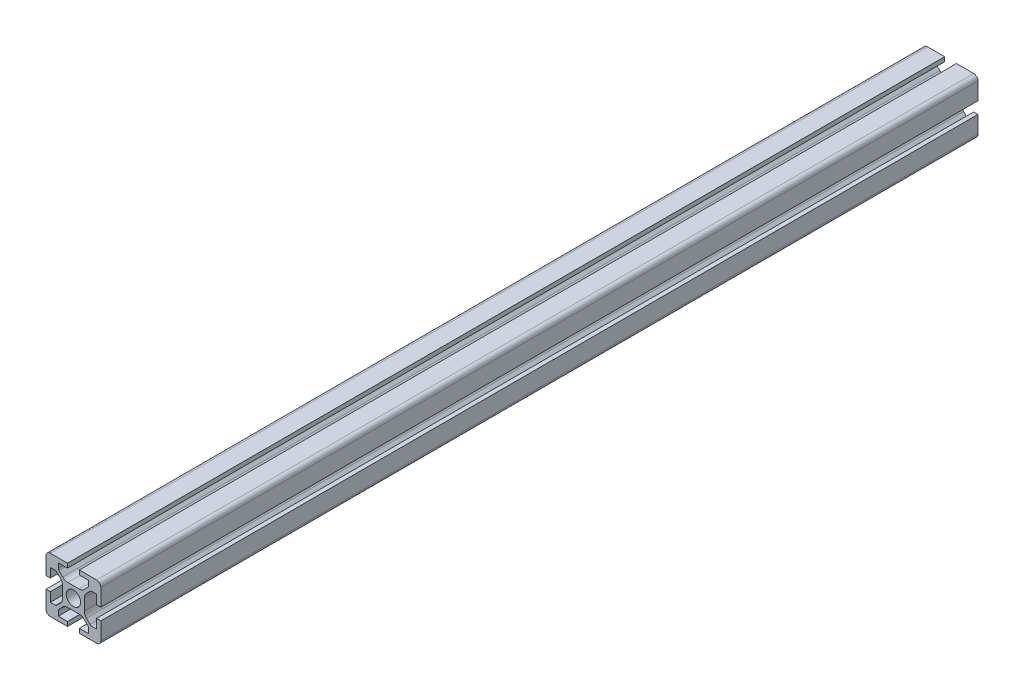
SolidWorks part; units mm, degrees
note: '?' marks a value the reader was unsure of.
ref_plane "Front Plane" through (0, 0, 0) normal (0, 0, 1) x (1, 0, 0)
ref_plane "Top Plane" through (0, 0, 0) normal (0, 1, 0) x (1, 0, 0)
ref_plane "Right Plane" through (0, 0, 0) normal (1, 0, 0) x (0, 0, -1)
sketch "Sketch1" plane through (0, 0, 0) normal (0, 0, 1) x (1, 0, 0)
  line L0 (-19.05, -4.1) -> (-19.05, -16.05)
  line L1 (-16.05, -19.05) -> (-4.1, -19.05)
  line L2 (-4.1, -19.05) -> (-4.1, -16.05)
  line L3 (-4.1, -16.05) -> (-10.5, -16.05)
  line L4 (-10.5, -16.05) -> (-10.5, -12.7127)
  line L5 (-10.0313, -11.5814) -> (-7.4645, -9.0145)
  line L6 (-3.9289, -7.55) -> (3.9289, -7.55)
  line L7 (7.4645, -9.0145) -> (10.0313, -11.5814)
  line L8 (10.5, -12.7127) -> (10.5, -16.05)
  line L9 (10.5, -16.05) -> (4.1, -16.05)
  line L10 (4.1, -16.05) -> (4.1, -19.05)
  line L11 (4.1, -19.05) -> (16.05, -19.05)
  line L12 (19.05, -16.05) -> (19.05, -4.1)
  line L13 (19.05, -4.1) -> (16.05, -4.1)
  line L14 (16.05, -4.1) -> (16.05, -10.5)
  line L15 (16.05, -10.5) -> (12.7127, -10.5)
  line L16 (11.5814, -10.0313) -> (9.0145, -7.4645)
  line L17 (7.55, -3.9289) -> (7.55, 3.9289)
  line L18 (9.0145, 7.4645) -> (11.5814, 10.0313)
  line L19 (12.7127, 10.5) -> (16.05, 10.5)
  line L20 (16.05, 10.5) -> (16.05, 4.1)
  line L21 (16.05, 4.1) -> (19.05, 4.1)
  line L22 (19.05, 4.1) -> (19.05, 16.05)
  line L23 (16.05, 19.05) -> (4.1, 19.05)
  line L24 (4.1, 19.05) -> (4.1, 16.05)
  line L25 (4.1, 16.05) -> (10.5, 16.05)
  line L26 (10.5, 16.05) -> (10.5, 12.7127)
  line L27 (10.0313, 11.5814) -> (7.4645, 9.0145)
  line L28 (3.9289, 7.55) -> (-3.9289, 7.55)
  line L29 (-7.4645, 9.0145) -> (-10.0313, 11.5814)
  line L30 (-10.5, 12.7127) -> (-10.5, 16.05)
  line L31 (-10.5, 16.05) -> (-4.1, 16.05)
  line L32 (-4.1, 16.05) -> (-4.1, 19.05)
  line L33 (-4.1, 19.05) -> (-16.05, 19.05)
  line L34 (-19.05, 16.05) -> (-19.05, 4.1)
  line L35 (-19.05, 4.1) -> (-16.05, 4.1)
  line L36 (-16.05, 4.1) -> (-16.05, 10.5)
  line L37 (-16.05, 10.5) -> (-12.7127, 10.5)
  line L38 (-11.5814, 10.0313) -> (-9.0145, 7.4645)
  line L39 (-7.55, 3.9289) -> (-7.55, -3.9289)
  line L40 (-9.0145, -7.4645) -> (-11.5814, -10.0313)
  line L41 (-12.7127, -10.5) -> (-16.05, -10.5)
  line L42 (-16.05, -10.5) -> (-16.05, -4.1)
  line L43 (-16.05, -4.1) -> (-19.05, -4.1)
  arc A0 (-19.05, -16.05) -> (-16.05, -19.05) centre (-16.05, -16.05) ccw
  arc A1 (-10.5, -12.7127) -> (-10.0313, -11.5814) centre (-8.9002, -12.7127) cw
  arc A2 (-7.4645, -9.0145) -> (-3.9289, -7.55) centre (-3.9289, -12.55) cw
  arc A3 (3.9289, -7.55) -> (7.4645, -9.0145) centre (3.9289, -12.55) cw
  arc A4 (10.0313, -11.5814) -> (10.5, -12.7127) centre (8.9002, -12.7127) cw
  arc A5 (16.05, -19.05) -> (19.05, -16.05) centre (16.05, -16.05) ccw
  arc A6 (12.7127, -10.5) -> (11.5814, -10.0313) centre (12.7127, -8.9002) cw
  arc A7 (9.0145, -7.4645) -> (7.55, -3.9289) centre (12.55, -3.9289) cw
  arc A8 (7.55, 3.9289) -> (9.0145, 7.4645) centre (12.55, 3.9289) cw
  arc A9 (11.5814, 10.0313) -> (12.7127, 10.5) centre (12.7127, 8.9002) cw
  arc A10 (19.05, 16.05) -> (16.05, 19.05) centre (16.05, 16.05) ccw
  arc A11 (10.5, 12.7127) -> (10.0313, 11.5814) centre (8.9002, 12.7127) cw
  arc A12 (7.4645, 9.0145) -> (3.9289, 7.55) centre (3.9289, 12.55) cw
  arc A13 (-3.9289, 7.55) -> (-7.4645, 9.0145) centre (-3.9289, 12.55) cw
  arc A14 (-10.0313, 11.5814) -> (-10.5, 12.7127) centre (-8.9002, 12.7127) cw
  arc A15 (-16.05, 19.05) -> (-19.05, 16.05) centre (-16.05, 16.05) ccw
  arc A16 (-12.7127, 10.5) -> (-11.5814, 10.0313) centre (-12.7127, 8.9002) cw
  arc A17 (-9.0145, 7.4645) -> (-7.55, 3.9289) centre (-12.55, 3.9289) cw
  arc A18 (-7.55, -3.9289) -> (-9.0145, -7.4645) centre (-12.55, -3.9289) cw
  arc A19 (-11.5814, -10.0313) -> (-12.7127, -10.5) centre (-12.7127, -8.9002) cw
  circle A20 centre (0, 0) radius 5
extrude "Boss-Extrude1" add sketch "Sketch1" along a picked direction on the side of the normal mid plane 609.6
sketch "Sketch2" plane through (0, 0, 0) normal (0, 0, 1) x (1, 0, 0)
  line L0 (-17.55, -12.5) -> (-17.55, -16.05)
  line L1 (-16.05, -17.55) -> (-12.5, -17.55)
  line L2 (-12, -17.05) -> (-12, -12.5)
  line L3 (-12.5, -12) -> (-17.05, -12)
  arc A0 (-17.55, -16.05) -> (-16.05, -17.55) centre (-16.05, -16.05) ccw
  arc A1 (-12.5, -17.55) -> (-12, -17.05) centre (-12.5, -17.05) ccw
  arc A2 (-12, -12.5) -> (-12.5, -12) centre (-12.5, -12.5) ccw
  arc A3 (-17.05, -12) -> (-17.55, -12.5) centre (-17.05, -12.5) ccw
sketch "Sketch3" plane through (0, 0, 0) normal (0, 0, 1) x (1, 0, 0)
  line L0 (12.5, -17.55) -> (16.05, -17.55)
  line L1 (17.55, -16.05) -> (17.55, -12.5)
  line L2 (17.05, -12) -> (12.5, -12)
  line L3 (12, -12.5) -> (12, -17.05)
  arc A0 (12, -17.05) -> (12.5, -17.55) centre (12.5, -17.05) ccw
  arc A1 (16.05, -17.55) -> (17.55, -16.05) centre (16.05, -16.05) ccw
  arc A2 (17.55, -12.5) -> (17.05, -12) centre (17.05, -12.5) ccw
  arc A3 (12.5, -12) -> (12, -12.5) centre (12.5, -12.5) ccw
sketch "Sketch4" plane through (0, 0, 0) normal (0, 0, 1) x (1, 0, 0)
  line L0 (-6.05, 1.0672) -> (-6.05, -1.191)
  line L1 (-6.05, -1.191) -> (-4.8565, -1.1891)
  line L2 (-4.2083, -2.7) -> (-6.05, -2.7)
  line L3 (-6.05, -2.7) -> (-6.05, -5.05)
  line L4 (-5.05, -6.05) -> (-2.7, -6.05)
  line L5 (-2.7, -6.05) -> (-2.7, -4.2083)
  line L6 (-1.15, -4.866) -> (-1.15, -6.05)
  line L7 (-1.15, -6.05) -> (1.15, -6.05)
  line L8 (1.15, -6.05) -> (1.15, -4.866)
  line L9 (2.7, -4.2083) -> (2.7, -6.05)
  line L10 (2.7, -6.05) -> (5.05, -6.05)
  line L11 (6.05, -5.05) -> (6.05, -2.7)
  line L12 (6.05, -2.7) -> (4.2083, -2.7)
  line L13 (4.8603, -1.1736) -> (6.05, -1.1717)
  line L14 (6.05, -1.1717) -> (6.05, 1.1063)
  line L15 (6.05, 1.1063) -> (4.8769, 1.1025)
  line L16 (4.2083, 2.7) -> (6.05, 2.7)
  line L17 (6.05, 2.7) -> (6.05, 5.05)
  line L18 (5.05, 6.05) -> (2.7, 6.05)
  line L19 (2.7, 6.05) -> (2.7, 4.2083)
  line L20 (1.15, 4.866) -> (1.15, 6.05)
  line L21 (1.15, 6.05) -> (-1.15, 6.05)
  line L22 (-1.15, 6.05) -> (-1.15, 4.866)
  line L23 (-2.7, 4.2083) -> (-2.7, 6.05)
  line L24 (-2.7, 6.05) -> (-5.05, 6.05)
  line L25 (-6.05, 5.05) -> (-6.05, 2.7)
  line L26 (-6.05, 2.7) -> (-4.2083, 2.7)
  line L27 (-4.8839, 1.071) -> (-6.05, 1.0672)
  arc A0 (-4.8565, -1.1891) -> (-4.2083, -2.7) centre (0, 0) ccw
  arc A1 (-6.05, -5.05) -> (-5.05, -6.05) centre (-5.05, -5.05) ccw
  arc A2 (-2.7, -4.2083) -> (-1.15, -4.866) centre (0, 0) ccw
  arc A3 (1.15, -4.866) -> (2.7, -4.2083) centre (0, 0) ccw
  arc A4 (5.05, -6.05) -> (6.05, -5.05) centre (5.05, -5.05) ccw
  arc A5 (4.2083, -2.7) -> (4.8603, -1.1736) centre (0, 0) ccw
  arc A6 (4.8769, 1.1025) -> (4.2083, 2.7) centre (0, 0) ccw
  arc A7 (6.05, 5.05) -> (5.05, 6.05) centre (5.05, 5.05) ccw
  arc A8 (2.7, 4.2083) -> (1.15, 4.866) centre (0, 0) ccw
  arc A9 (-1.15, 4.866) -> (-2.7, 4.2083) centre (0, 0) ccw
  arc A10 (-5.05, 6.05) -> (-6.05, 5.05) centre (-5.05, 5.05) ccw
  arc A11 (-4.2083, 2.7) -> (-4.8839, 1.071) centre (0, 0) ccw
sketch "Sketch5" plane through (0, 0, 0) normal (0, 0, 1) x (1, 0, 0)
  line L0 (12, 17.05) -> (12, 12.5)
  line L1 (12.5, 12) -> (17.05, 12)
  line L2 (17.55, 12.5) -> (17.55, 16.05)
  line L3 (16.05, 17.55) -> (12.5, 17.55)
  arc A0 (12, 12.5) -> (12.5, 12) centre (12.5, 12.5) ccw
  arc A1 (17.05, 12) -> (17.55, 12.5) centre (17.05, 12.5) ccw
  arc A2 (17.55, 16.05) -> (16.05, 17.55) centre (16.05, 16.05) ccw
  arc A3 (12.5, 17.55) -> (12, 17.05) centre (12.5, 17.05) ccw
sketch "Sketch6" plane through (0, 0, 0) normal (0, 0, 1) x (1, 0, 0)
  line L0 (-17.05, 12) -> (-12.5, 12)
  line L1 (-12, 12.5) -> (-12, 17.05)
  line L2 (-12.5, 17.55) -> (-16.05, 17.55)
  line L3 (-17.55, 16.05) -> (-17.55, 12.5)
  arc A0 (-17.55, 12.5) -> (-17.05, 12) centre (-17.05, 12.5) ccw
  arc A1 (-12.5, 12) -> (-12, 12.5) centre (-12.5, 12.5) ccw
  arc A2 (-12, 17.05) -> (-12.5, 17.55) centre (-12.5, 17.05) ccw
  arc A3 (-16.05, 17.55) -> (-17.55, 16.05) centre (-16.05, 16.05) ccw
extrude "Cut-Extrude1" cut sketch "Sketch2" against normal blind 6000
extrude "Cut-Extrude2" cut sketch "Sketch3" against normal blind 6000
extrude "Cut-Extrude3" cut sketch "Sketch4" against normal blind 6000
extrude "Cut-Extrude4" cut sketch "Sketch5" against normal blind 6000
extrude "Cut-Extrude5" cut sketch "Sketch6" against normal blind 6000
ref_plane "Plane1" through (0, 19.05, 0) normal (0, 1, 0) x (-1, 0, 0)
ref_plane "Plane2" through (0, -19.05, 0) normal (0, -1, 0) x (1, 0, 0)
ref_plane "Plane3" through (19.05, 0, 0) normal (1, 0, 0) x (0, 0, -1)
ref_plane "Plane4" through (-19.05, 0, 0) normal (-1, 0, 0) x (0, 0, 1)
ref_plane "Plane5" through (0, 0, 0) normal (0, 0, 1) x (1, 0, 0)
ref_plane "Plane6" through (0, 0, 0) normal (0, 0, 1) x (1, 0, 0)
ref_plane "Plane7" through (0, 0, 0) normal (0, 0, 1) x (1, 0, 0)
ref_plane "Plane8" through (0, 0, -50) normal (0, 0, 1) x (1, 0, 0)
ref_plane "Plane9" through (0, 0, -50) normal (0, 0, 1) x (1, 0, 0)
ref_plane "Plane10" through (0, 0, -50) normal (0, 0, 1) x (1, 0, 0)
ref_plane "side_4d XY" through (0, 0, 0) normal (0, 0, 1) x (1, 0, 0)
ref_plane "side_4d XZ" through (-19.05, 0, 0) normal (-1, 0, 0) x (0, 0, 1)
ref_plane "side_4d YZ" through (0, 0, 0) normal (0, -1, 0) x (1, 0, 0)
ref_axis "side_4d X" through (-19.05, 50, 0) along (0, -1, 0)?
ref_axis "side_4d Y" through (-80.9, 0, 0) along (1, 0, 0)?
ref_axis "side_4d Z" through (-19.05, 0, 50) along (0, 0, -1)?
sketch3d "side_4d"
  point P0 (-19.05, 0, 0)
ref_plane "side_1a XY" through (0, 0, 0) normal (0, 0, 1) x (1, 0, 0)
ref_plane "side_1a XZ" through (0, 19.05, 0) normal (0, -1, 0) x (1, 0, 0)
ref_plane "side_1a YZ" through (0, 0, 0) normal (1, 0, 0) x (0, 0, -1)
ref_axis "side_1a X" through (-80.9, 19.05, 0) along (1, 0, 0)?
ref_axis "side_1a Y" through (0, -50, 0) along (0, 1, 0)?
ref_axis "side_1a Z" through (0, 19.05, 80.9) along (0, 0, -1)?
sketch3d "side_1a"
  point P0 (0, 19.05, 0)
ref_plane "side_2b XY" through (0, 0, 0) normal (0, 0, 1) x (1, 0, 0)
ref_plane "side_2b XZ" through (19.05, 0, 0) normal (1, 0, 0) x (0, 0, -1)
ref_plane "side_2b YZ" through (0, 0, 0) normal (0, 1, 0) x (-1, 0, 0)
ref_axis "side_2b X" through (19.05, -50, 0) along (0, 1, 0)?
ref_axis "side_2b Y" through (80.9, 0, 0) along (-1, 0, 0)?
ref_axis "side_2b Z" through (19.05, 0, 50) along (0, 0, -1)?
sketch3d "side_2b"
  point P0 (19.05, 0, 0)
ref_plane "side_3c XY" through (0, 0, 0) normal (0, 0, 1) x (1, 0, 0)
ref_plane "side_3c XZ" through (0, -19.05, 0) normal (0, 1, 0) x (-1, 0, 0)
ref_plane "side_3c YZ" through (0, 0, 0) normal (-1, 0, 0) x (0, 0, 1)
ref_axis "side_3c X" through (80.9, -19.05, 0) along (-1, 0, 0)?
ref_axis "side_3c Y" through (0, 50, 0) along (0, -1, 0)?
ref_axis "side_3c Z" through (0, -19.05, 80.9) along (0, 0, -1)?
sketch3d "side_3c"
  point P0 (0, -19.05, 0)
ref_plane "start XY" through (0, 0, 0) normal (0, 0, 1) x (1, 0, 0)
ref_plane "start XZ" through (0, 0, 0) normal (0, -1, 0) x (1, 0, 0)
ref_plane "start YZ" through (0, 0, 0) normal (1, 0, 0) x (0, 0, -1)
ref_axis "start X" through (-80.9, 0, 0) along (1, 0, 0)?
ref_axis "start Y" through (0, -50, 0) along (0, 1, 0)?
ref_axis "start Z" through (0, 0, 80.9) along (0, 0, -1)?
sketch3d "start"
  point P0 (0, 0, 0)
ref_plane "end XY" through (0, 0, -50) normal (0, 0, -1) x (-1, 0, 0)
ref_plane "end XZ" through (0, 0, 0) normal (0, 1, 0) x (-1, 0, 0)
ref_plane "end YZ" through (0, 0, 0) normal (1, 0, 0) x (0, 0, -1)
ref_axis "end X" through (-80.9, 0, -50) along (1, 0, 0)?
ref_axis "end Y" through (0, 50, -50) along (0, -1, 0)?
ref_axis "end Z" through (0, 0, -80.9) along (0, 0, 1)?
sketch3d "end"
  point P0 (0, 0, -50)
